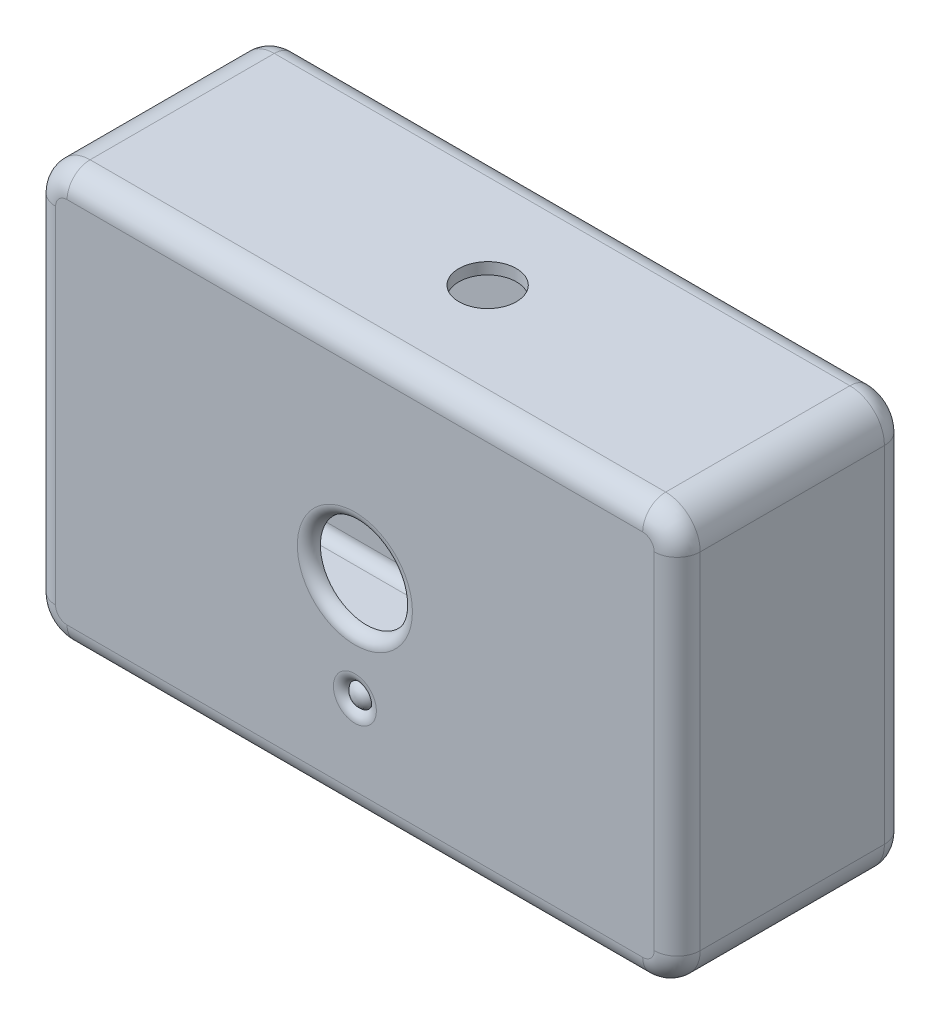
SolidWorks part; units mm, degrees
ref_plane "Alzado" through (0, 0, 0) normal (0, 0, 1) x (1, 0, 0)
ref_plane "Planta" through (0, 0, 0) normal (0, 1, 0) x (1, 0, 0)
ref_plane "Vista lateral" through (0, 0, 0) normal (1, 0, 0) x (0, 0, -1)
sketch "Croquis2" plane through (0, 0, 0) normal (0, 0, 1) x (1, 0, 0)
  line L1 (-25, -18) -> (25, -18)
  line L2 (-28, -15) -> (-28, 15)
  line L3 (-25, 18) -> (25, 18)
  line L4 (28, -15) -> (28, 15)
  line L5 (-28, -18) -> (28, 18) construction
  line L6 (-28, 18) -> (28, -18) construction
  arc A0 (25, -18) -> (28, -15) centre (25, -15) ccw
  arc A1 (-25, -18) -> (-28, -15) centre (-25, -15) cw
  arc A2 (-25, 18) -> (-28, 15) centre (-25, 15) ccw
  arc A3 (25, 18) -> (28, 15) centre (25, 15) cw
  point P0 (0, 0)
  dimension "D1" = 3
extrude "Saliente-Extruir1" add sketch "Croquis2" along normal blind 20
fillet "Redondeo1" radius 2 16 edges at (0, -18, 20) (-27.1213, -17.1213, 20) (-28, 0, 20) (-27.1213, 17.1213, 20) (0, 18, 20) (27.1213, 17.1213, 20) (28, 0, 20) (27.1213, -17.1213, 20) (28, 0, 0) (27.1213, -17.1213, 0) (0, -18, 0) (-27.1213, -17.1213, 0) (-28, 0, 0) (-27.1213, 17.1213, 0) (0, 18, 0) (27.1213, 17.1213, 0)
shell "Vaciado1" thickness 1 removed face at (0, 0, 20)
ref_plane "Plano1" through (0, 0, 20) normal (0, 0, 1) x (1, 0, 0)
sketch "Croquis3" plane through (0, 0, 20) normal (0, 0, 1) x (1, 0, 0)
  line L25 (26, 15) -> (26, -15)
  line L26 (25, -16) -> (-25, -16)
  line L27 (-26, -15) -> (-26, 15)
  line L28 (-25, 16) -> (25, 16)
  line L29 (26, 15) -> (26, -15)
  line L30 (25, -16) -> (-25, -16)
  line L31 (-26, -15) -> (-26, 15)
  line L32 (-25, 16) -> (25, 16)
  arc A12 (-25, -16) -> (-26, -15) centre (-25, -15) cw
  arc A15 (26, 15) -> (25, 16) centre (25, 15) ccw
  arc A16 (25, -16) -> (26, -15) centre (25, -15) ccw
  arc A17 (-25, 16) -> (-26, 15) centre (-25, 15) ccw
  arc A18 (26, 15) -> (25, 16) centre (25, 15) ccw
  arc A19 (25, -16) -> (26, -15) centre (25, -15) ccw
  arc A20 (-25, 16) -> (-26, 15) centre (-25, 15) ccw
  dimension "D1" = 0
extrude "Saliente-Extruir2" add sketch "Croquis3" against normal blind 1
sketch "Croquis4" plane through (0, 0, 20) normal (0, 0, 1) x (1, 0, 0)
  circle A0 centre (0, 0) radius 4
extrude "Cortar-Extruir1" cut sketch "Croquis4" against normal blind 1
fillet "Redondeo2" radius 1 1 edges at (4, 0, 20)
sketch "Croquis5" plane through (0, 0, 20) normal (0, 0, 1) x (1, 0, 0)
  line L0 (0, -11) -> (0, 11) construction
  circle A0 centre (0, -9.0317) radius 1
extrude "Cortar-Extruir2" cut sketch "Croquis5" against normal blind 0.5
sketch "Croquis12" plane through (0, 0, 0) normal (1, 0, 0) x (0, 0, -1)
  line L0 (-19.5, -8.0317) -> (-19.5, -10.0317) construction
  line L1 (-20, 19.8) -> (-20, -19.8) construction
  line L2 (-20, -9.0317) -> (-19.5, -9.0317)
  line L3 (-19.5, -9.0317) -> (-19.5, -8.0317)
  line L4 (-19.5, -9.0317) -> (-20.3751, -9.0317) construction
  arc A0 (-19.5, -8.0317) -> (-20, -9.0317) centre (-18.8287, -8.9924) ccw
revolve "Revolución1" add sketch "Croquis12" angle 360 about L4
fillet "Redondeo3" radius 1 1 edges at (1, -9.0317, 20)
sketch "Croquis13" plane through (0, 18, 0) normal (0, 1, 0) x (1, 0, 0)
  circle A0 centre (1.6967, -10.1655) radius 2.5
extrude "Cortar-Extruir3" cut sketch "Croquis13" against normal blind 1
